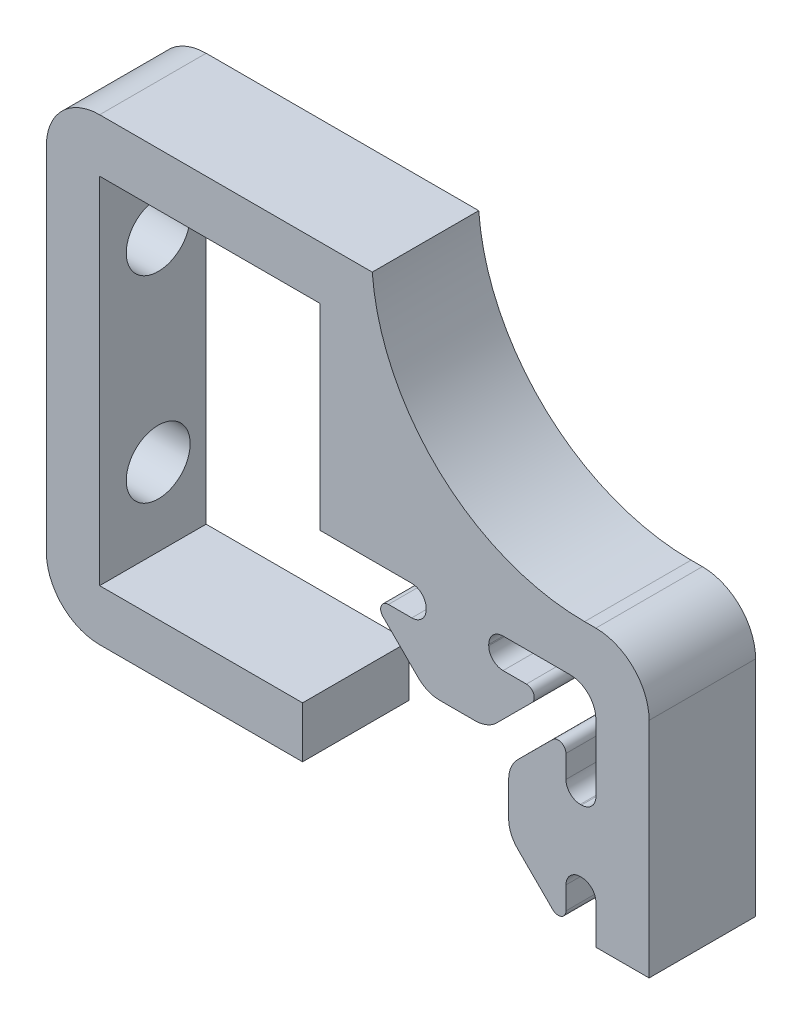
SolidWorks part; units mm, degrees
ref_plane "Front Plane" through (0, 0, 0) normal (0, 0, 1) x (1, 0, 0)
ref_plane "Top Plane" through (0, 0, 0) normal (0, 1, 0) x (1, 0, 0)
ref_plane "Right Plane" through (0, 0, 0) normal (1, 0, 0) x (0, 0, -1)
sketch "Sketch1" plane through (0, 0, 0) normal (0, 0, 1) x (1, 0, 0)
  line L1 (-4.3059, -13) -> (-4.2875, -13)
  line L11 (13, -7.9544) -> (13, -5.3171)
  line L12 (13, -5.3171) -> (13, -4.2875)
  line L13 (11.651, -2.9385) -> (11.5392, -2.9385)
  line L14 (10.1902, -4.2875) -> (10.1902, -6.4021)
  line L15 (8.949, -6.917) -> (5.6529, -3.6284)
  line L16 (4.8085, -1.5932) -> (4.8085, 1.5932)
  line L17 (5.6529, 3.6284) -> (8.949, 6.917)
  line L18 (10.1902, 6.4021) -> (10.1902, 4.2875)
  line L19 (11.5392, 2.9385) -> (11.651, 2.9385)
  line L20 (13, 4.2875) -> (13, 5.3171)
  line L21 (13, 7.9544) -> (13, 10.5918)
  line L22 (10.5918, 13) -> (5.3216, 13)
  line L23 (5.3216, 13) -> (4.2875, 13)
  line L24 (2.9385, 11.651) -> (2.9385, 11.5392)
  line L25 (4.2875, 10.1902) -> (6.4768, 10.1902)
  line L26 (6.9951, 8.9367) -> (3.6864, 5.6355)
  line L27 (1.6558, 4.7958) -> (-1.6558, 4.7958)
  line L28 (-3.6864, 5.6355) -> (-6.9951, 8.9367)
  line L29 (-6.4768, 10.1902) -> (-4.2875, 10.1902)
  line L30 (-2.9385, 11.5392) -> (-2.9385, 11.651)
  line L31 (-4.2875, 13) -> (-4.3059, 13)
  line L32 (-4.3059, 13) -> (-12.9, 13)
  line L33 (-13, 10.5918) -> (-13, 5.3171) construction
  line L34 (-13, 5.3171) -> (-13, 4.2875) construction
  line L35 (-11.651, 2.9385) -> (-11.5392, 2.9385) construction
  line L36 (-10.1902, 4.2875) -> (-10.1902, 6.4021) construction
  line L37 (-8.949, 6.917) -> (-5.6529, 3.6284) construction
  line L38 (-4.8085, 1.5932) -> (-4.8085, -1.5932) construction
  line L39 (-5.6529, -3.6284) -> (-8.949, -6.917) construction
  line L40 (-10.1902, -6.4021) -> (-10.1902, -4.2875) construction
  line L41 (-11.5392, -2.9385) -> (-11.651, -2.9385) construction
  line L43 (18, -7.9544) -> (18, 18)
  line L44 (13, 5.3171) -> (13, 7.9544)
  line L45 (-33.4, 31.3527) -> (-13, 31.3527) construction
  line L46 (-33.4, 31.3527) -> (-33.4, -1.6473) construction
  line L47 (-33.4, -1.6473) -> (-13, -1.6473) construction
  line L48 (-13, 31.3527) -> (-13, -1.6473) construction
  line L53 (-18, -6.6473) -> (-38.6, -6.6473)
  line L54 (-38.6, -6.6473) -> (-38.6, 36.4527)
  line L55 (-38.6, 36.4527) -> (-8, 36.4527)
  line L57 (-12.9, 31.4527) -> (-33.6, 31.4527)
  line L58 (-33.6, 31.4527) -> (-33.6, -1.8473)
  line L59 (-33.6, -1.8473) -> (-14.5421, -1.8473)
  line L61 (18, 18) -> (-8, 18)
  line L62 (-8, 18) -> (-8, 36.4527)
  line L63 (13, -7.9544) -> (18, -7.9544)
  line L64 (-12.9, 31.4527) -> (-12.9, 13)
  line L65 (-4.3059, 13) -> (-10.5918, 13) construction
  line L66 (-18, -6.6473) -> (-14.5421, -6.6473)
  line L67 (-14.5421, -6.6473) -> (-14.5421, -1.8473)
  line L68 (13, -10.5918) -> (13, -5.3171) construction
  line L88 (-7.1797, -8.6452) -> (-3.9523, -5.4237) construction
  line L89 (-1.7093, -4.4958) -> (1.7093, -4.4958) construction
  line L90 (3.9523, -5.4237) -> (7.1797, -8.6452) construction
  line L91 (6.4164, -10.4902) -> (4.2875, -10.4902) construction
  line L92 (3.2385, -11.5392) -> (3.2385, -11.651) construction
  line L93 (4.2875, -12.7) -> (5.3216, -12.7) construction
  line L94 (5.3216, -12.7) -> (10.5918, -12.7) construction
  line L95 (12.7, -10.5918) -> (12.7, -5.3171) construction
  line L96 (12.7, -5.3171) -> (12.7, -4.2875) construction
  line L97 (11.651, -3.2385) -> (11.5392, -3.2385) construction
  line L98 (10.4902, -4.2875) -> (10.4902, -6.4021) construction
  line L99 (8.7371, -7.1294) -> (5.441, -3.8408) construction
  line L100 (4.5085, -1.5932) -> (4.5085, 1.5932) construction
  line L101 (5.441, 3.8408) -> (8.7371, 7.1294) construction
  line L102 (10.4902, 6.4021) -> (10.4902, 4.2875) construction
  line L103 (11.5392, 3.2385) -> (11.651, 3.2385) construction
  line L104 (12.7, 4.2875) -> (12.7, 5.3171) construction
  line L105 (12.7, 5.3171) -> (12.7, 10.5918) construction
  line L106 (10.5918, 12.7) -> (5.3216, 12.7) construction
  line L107 (5.3216, 12.7) -> (4.2875, 12.7) construction
  line L108 (3.2385, 11.651) -> (3.2385, 11.5392) construction
  line L109 (4.2875, 10.4902) -> (6.4768, 10.4902) construction
  line L110 (7.207, 8.7244) -> (3.8983, 5.4232) construction
  line L111 (1.6558, 4.4958) -> (-1.6558, 4.4958) construction
  line L112 (-3.8983, 5.4232) -> (-7.207, 8.7244) construction
  line L113 (-6.4768, 10.4902) -> (-4.2875, 10.4902) construction
  line L114 (-3.2385, 11.5392) -> (-3.2385, 11.651) construction
  line L115 (-4.2875, 12.7) -> (-4.3059, 12.7) construction
  line L116 (-4.3059, 12.7) -> (-10.5918, 12.7) construction
  line L117 (-12.7, 10.5918) -> (-12.7, 5.3171) construction
  line L118 (-12.7, 5.3171) -> (-12.7, 4.2875) construction
  line L119 (-11.651, 3.2385) -> (-11.5392, 3.2385) construction
  line L120 (-10.4902, 4.2875) -> (-10.4902, 6.4021) construction
  line L121 (-8.7371, 7.1294) -> (-5.441, 3.8408) construction
  line L122 (-4.5085, 1.5932) -> (-4.5085, -1.5932) construction
  line L123 (-5.441, -3.8408) -> (-8.7371, -7.1294) construction
  line L124 (-10.4902, -6.4021) -> (-10.4902, -4.2875) construction
  line L125 (-11.5392, -3.2385) -> (-11.651, -3.2385) construction
  line L126 (-12.7, -4.2875) -> (-12.7, -5.3171) construction
  line L127 (-12.7, -5.3171) -> (-12.7, -10.5918) construction
  line L128 (-10.5918, -12.7) -> (-4.3059, -12.7) construction
  line L129 (-4.3059, -12.7) -> (-4.2875, -12.7) construction
  line L130 (-3.2385, -11.651) -> (-3.2385, -11.5392) construction
  line L131 (-4.2875, -10.4902) -> (-6.4164, -10.4902) construction
  line L132 (-13, -4.2875) -> (-13, -5.3171) construction
  line L133 (-13, -5.3171) -> (-13, -10.5918) construction
  line L134 (-10.5918, -13) -> (-4.3059, -13) construction
  line L135 (-4.2875, -10.1902) -> (-6.4164, -10.1902) construction
  line L136 (-6.9677, -8.8575) -> (-3.7403, -5.636) construction
  line L137 (-1.7093, -4.7958) -> (1.7093, -4.7958) construction
  line L138 (3.7403, -5.636) -> (6.9677, -8.8575) construction
  line L139 (6.4164, -10.1902) -> (4.2875, -10.1902) construction
  line L140 (2.9385, -11.5392) -> (2.9385, -11.651) construction
  line L141 (4.2875, -13) -> (5.3216, -13) construction
  line L142 (5.3216, -13) -> (10.5918, -13) construction
  line L143 (-2.9385, -11.651) -> (-2.9385, -11.5392) construction
  line L144 (13, 5.3171) -> (13, 10.5918) construction
  arc A4 (-1.7093, -4.7958) -> (-3.7403, -5.636) centre (-1.7093, -7.6708) ccw
  arc A9 (13, -4.2875) -> (11.651, -2.9385) centre (11.651, -4.2875) ccw
  arc A10 (11.5392, -2.9385) -> (10.1902, -4.2875) centre (11.5392, -4.2875) ccw
  arc A11 (8.949, -6.917) -> (10.1902, -6.4021) centre (9.4628, -6.4021) ccw
  arc A12 (4.8085, -1.5932) -> (5.6529, -3.6284) centre (7.6835, -1.5932) ccw
  arc A13 (5.6529, 3.6284) -> (4.8085, 1.5932) centre (7.6835, 1.5932) ccw
  arc A14 (10.1902, 6.4021) -> (8.949, 6.917) centre (9.4628, 6.4021) ccw
  arc A15 (10.1902, 4.2875) -> (11.5392, 2.9385) centre (11.5392, 4.2875) ccw
  arc A16 (11.651, 2.9385) -> (13, 4.2875) centre (11.651, 4.2875) ccw
  arc A17 (4.2875, 13) -> (2.9385, 11.651) centre (4.2875, 11.651) ccw
  arc A18 (2.9385, 11.5392) -> (4.2875, 10.1902) centre (4.2875, 11.5392) ccw
  arc A19 (6.9951, 8.9367) -> (6.4768, 10.1902) centre (6.4768, 9.4563) ccw
  arc A20 (1.6558, 4.7958) -> (3.6864, 5.6355) centre (1.6558, 7.6708) ccw
  arc A21 (-3.6864, 5.6355) -> (-1.6558, 4.7958) centre (-1.6558, 7.6708) ccw
  arc A22 (-6.4768, 10.1902) -> (-6.9951, 8.9367) centre (-6.4768, 9.4563) ccw
  arc A23 (-4.2875, 10.1902) -> (-2.9385, 11.5392) centre (-4.2875, 11.5392) ccw
  arc A24 (-2.9385, 11.651) -> (-4.2875, 13) centre (-4.2875, 11.651) ccw
  arc A25 (-13, 4.2875) -> (-11.651, 2.9385) centre (-11.651, 4.2875) ccw construction
  arc A26 (-11.5392, 2.9385) -> (-10.1902, 4.2875) centre (-11.5392, 4.2875) ccw construction
  arc A27 (-8.949, 6.917) -> (-10.1902, 6.4021) centre (-9.4628, 6.4021) ccw construction
  arc A28 (-4.8085, 1.5932) -> (-5.6529, 3.6284) centre (-7.6835, 1.5932) ccw construction
  arc A29 (-5.6529, -3.6284) -> (-4.8085, -1.5932) centre (-7.6835, -1.5932) ccw construction
  arc A30 (-10.1902, -6.4021) -> (-8.949, -6.917) centre (-9.4628, -6.4021) ccw construction
  arc A31 (-10.1902, -4.2875) -> (-11.5392, -2.9385) centre (-11.5392, -4.2875) ccw construction
  arc A32 (-11.651, -2.9385) -> (-13, -4.2875) centre (-11.651, -4.2875) ccw construction
  arc A34 (13, 10.5918) -> (10.5628, 12.9998) centre (10.5918, 10.5918) ccw
  arc A35 (-10.5628, 12.9998) -> (-12.9998, 10.5628) centre (-10.5918, 10.5918) ccw construction
  arc A37 (12.9998, 10.5628) -> (10.5628, 12.9998) centre (10.5918, 10.5918) ccw construction
  arc A104 (-7.1797, -8.6452) -> (-6.4164, -10.4902) centre (-6.4164, -9.4098) ccw construction
  arc A105 (-1.7093, -4.4958) -> (-3.9523, -5.4237) centre (-1.7093, -7.6708) ccw construction
  arc A106 (3.9523, -5.4237) -> (1.7093, -4.4958) centre (1.7093, -7.6708) ccw construction
  arc A107 (6.4164, -10.4902) -> (7.1797, -8.6452) centre (6.4164, -9.4098) ccw construction
  arc A108 (4.2875, -10.4902) -> (3.2385, -11.5392) centre (4.2875, -11.5392) ccw construction
  arc A109 (3.2385, -11.651) -> (4.2875, -12.7) centre (4.2875, -11.651) ccw construction
  arc A112 (10.5664, -12.6998) -> (12.6998, -10.5664) centre (10.5918, -10.5918) ccw construction
  arc A115 (12.7, -4.2875) -> (11.651, -3.2385) centre (11.651, -4.2875) ccw construction
  arc A116 (11.5392, -3.2385) -> (10.4902, -4.2875) centre (11.5392, -4.2875) ccw construction
  arc A117 (8.7371, -7.1294) -> (10.4902, -6.4021) centre (9.4628, -6.4021) ccw construction
  arc A118 (4.5085, -1.5932) -> (5.441, -3.8408) centre (7.6835, -1.5932) ccw construction
  arc A119 (5.441, 3.8408) -> (4.5085, 1.5932) centre (7.6835, 1.5932) ccw construction
  arc A120 (10.4902, 6.4021) -> (8.7371, 7.1294) centre (9.4628, 6.4021) ccw construction
  arc A121 (10.4902, 4.2875) -> (11.5392, 3.2385) centre (11.5392, 4.2875) ccw construction
  arc A122 (11.651, 3.2385) -> (12.7, 4.2875) centre (11.651, 4.2875) ccw construction
  arc A125 (12.6998, 10.5664) -> (10.5664, 12.6998) centre (10.5918, 10.5918) ccw construction
  arc A128 (4.2875, 12.7) -> (3.2385, 11.651) centre (4.2875, 11.651) ccw construction
  arc A129 (3.2385, 11.5392) -> (4.2875, 10.4902) centre (4.2875, 11.5392) ccw construction
  arc A130 (7.207, 8.7244) -> (6.4768, 10.4902) centre (6.4768, 9.4563) ccw construction
  arc A131 (1.6558, 4.4958) -> (3.8983, 5.4232) centre (1.6558, 7.6708) ccw construction
  arc A132 (-3.8983, 5.4232) -> (-1.6558, 4.4958) centre (-1.6558, 7.6708) ccw construction
  arc A133 (-6.4768, 10.4902) -> (-7.207, 8.7244) centre (-6.4768, 9.4563) ccw construction
  arc A134 (-4.2875, 10.4902) -> (-3.2385, 11.5392) centre (-4.2875, 11.5392) ccw construction
  arc A135 (-3.2385, 11.651) -> (-4.2875, 12.7) centre (-4.2875, 11.651) ccw construction
  arc A138 (-10.5664, 12.6998) -> (-12.6998, 10.5664) centre (-10.5918, 10.5918) ccw construction
  arc A141 (-12.7, 4.2875) -> (-11.651, 3.2385) centre (-11.651, 4.2875) ccw construction
  arc A142 (-11.5392, 3.2385) -> (-10.4902, 4.2875) centre (-11.5392, 4.2875) ccw construction
  arc A143 (-8.7371, 7.1294) -> (-10.4902, 6.4021) centre (-9.4628, 6.4021) ccw construction
  arc A144 (-4.5085, 1.5932) -> (-5.441, 3.8408) centre (-7.6835, 1.5932) ccw construction
  arc A145 (-5.441, -3.8408) -> (-4.5085, -1.5932) centre (-7.6835, -1.5932) ccw construction
  arc A146 (-10.4902, -6.4021) -> (-8.7371, -7.1294) centre (-9.4628, -6.4021) ccw construction
  arc A147 (-10.4902, -4.2875) -> (-11.5392, -3.2385) centre (-11.5392, -4.2875) ccw construction
  arc A148 (-11.651, -3.2385) -> (-12.7, -4.2875) centre (-11.651, -4.2875) ccw construction
  arc A151 (-12.6998, -10.5664) -> (-10.5918, -12.7) centre (-10.5918, -10.5918) ccw construction
  arc A154 (-4.2875, -12.7) -> (-3.2385, -11.651) centre (-4.2875, -11.651) ccw construction
  arc A155 (-3.2385, -11.5392) -> (-4.2875, -10.4902) centre (-4.2875, -11.5392) ccw construction
  arc A156 (-4.2875, -13) -> (-2.9385, -11.651) centre (-4.2875, -11.651) ccw construction
  arc A157 (-2.9385, -11.5392) -> (-4.2875, -10.1902) centre (-4.2875, -11.5392) ccw construction
  arc A158 (-6.9677, -8.8575) -> (-6.4164, -10.1902) centre (-6.4164, -9.4098) ccw construction
  arc A159 (3.7403, -5.636) -> (1.7093, -4.7958) centre (1.7093, -7.6708) ccw construction
  arc A160 (6.4164, -10.1902) -> (6.9677, -8.8575) centre (6.4164, -9.4098) ccw construction
  arc A161 (4.2875, -10.1902) -> (2.9385, -11.5392) centre (4.2875, -11.5392) ccw construction
  arc A162 (2.9385, -11.651) -> (4.2875, -13) centre (4.2875, -11.651) ccw construction
  dimension "D2" = 33
  dimension "D3" = 20.4
  dimension "D4" = 5
  dimension "D5" = 5
  dimension "D6" = 5
  dimension "D7" = 0.2
  dimension "D9" = 5
  dimension "D10" = 5
  dimension "D11" = 5
  dimension "D12" = 0.2
  dimension "D13" = 0.2
  dimension ".2" = 0.2
  dimension "D1" = 0.3
extrude "Boss-Extrude1" add sketch "Sketch1" along normal blind 10 contours L59 L58 L57 L55 L54 L53 L44 L20 A16 L19 A15 L18 A14 L17 A13 L16 A12 L15 A11 L14 A10 L13 A9 L12 L11 A4 region at (-11.6511, 13.3006, 0)
sketch "Sketch2" plane through (-38.6, 0, 0) normal (-1, 0, 0) x (0, 0, 1)
  line L0 (0, -6.6473) -> (0, 36.4527) construction
  line L3 (4.5, 26.9527) -> (4.5, 23.9527) construction
  line L4 (10, 31.4527) -> (0, 31.4527) construction
  line L5 (4.5, 8.4527) -> (4.5, 2.4527) construction
  line L6 (4.5, 23.9527) -> (4.5, 20.9527) construction
  circle A0 centre (4.5, 23.9527) radius 3
  circle A1 centre (4.5, 5.4527) radius 3
  dimension "D1" = 6
  dimension "D3" = 6
  dimension "D2" = 7.5
  dimension "D4" = 12.5
  dimension "D5" = 4.5
extrude "Cut-Extrude1" cut sketch "Sketch2" against normal up to next
fillet "Fillet1" radius 20 1 edges at (-8, 18, 5)
fillet "Fillet2" radius 5 3 edges at (-38.6, -6.6473, 5) (18, 18, 5) (-38.6, 36.4527, 5)
